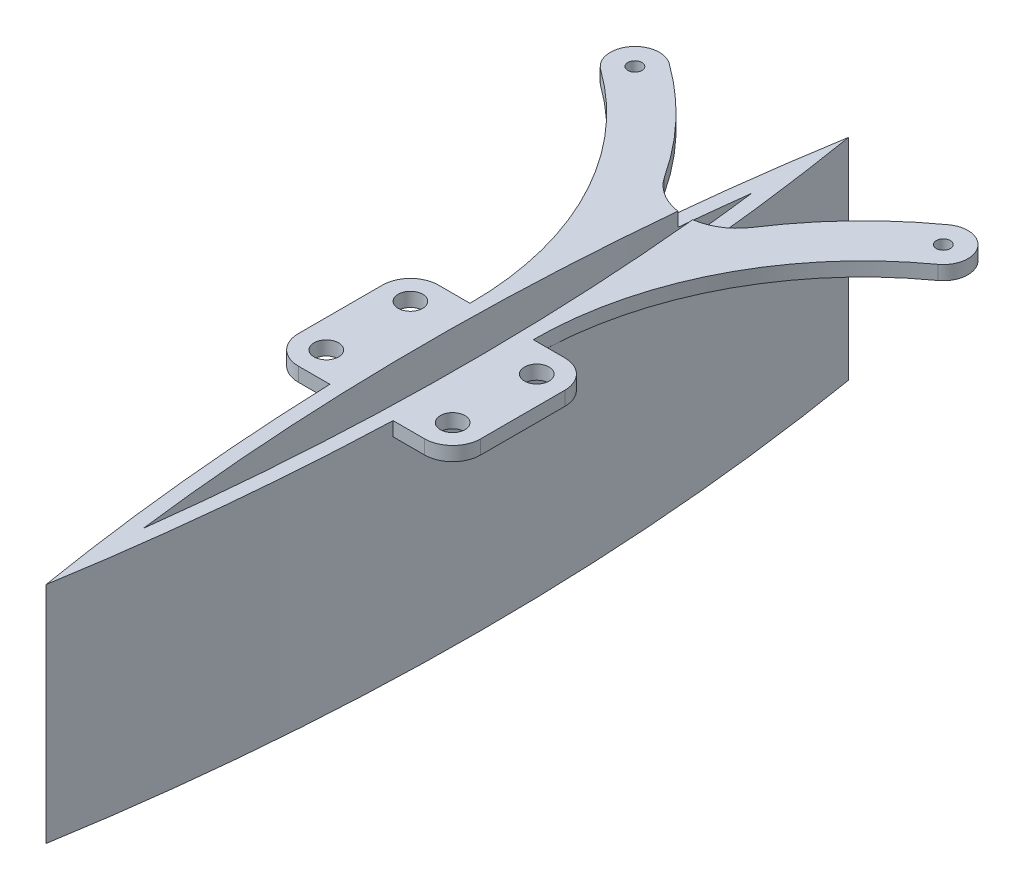
SolidWorks part; units mm, degrees
ref_plane "Plan de face" through (0, 0, 0) normal (0, 0, 1) x (1, 0, 0)
ref_plane "Plan de dessus" through (0, 0, 0) normal (0, 1, 0) x (1, 0, 0)
ref_plane "Plan de droite" through (0, 0, 0) normal (1, 0, 0) x (0, 0, -1)
sketch "Esquisse1" plane through (-102.8474, 0, 18.1348) normal (0, -1, 0) x (-0.9359, 0, 0.3523)
  line L0 (-4.457, -64.9899) -> (-37.8828, 23.8081) construction
  line L1 (-35.783, -7.317) -> (-31.5715, -5.7317)
  line L2 (-18.929, -0.997) -> (-23.1405, -2.5823)
  line L3 (-30.1464, -22.2913) -> (-17.5198, -4.7406) construction
  line L4 (-122.0187, 32.2138) -> (-83.2665, -70.7341) construction
  line L7 (-33.8899, -23.7004) -> (-38.1174, -12.4698)
  line L9 (-24.5257, -24.4495) -> (-28.7372, -26.0348)
  line L11 (-13.7762, -3.3314) -> (-9.5488, -14.5621)
  line L12 (-11.8832, -19.7148) -> (-16.0947, -21.3001)
  line L14 (-65.4719, 25.3159) -> (-23.8989, 40.965) construction
  line L15 (-37.8828, 23.8081) -> (-43.0375, 37.5019) construction
  line L16 (-24.5257, -24.4495) -> (-31.5715, -5.7317) construction
  line L17 (-23.1405, -2.5823) -> (-16.0947, -21.3001) construction
  arc A1 (-24.5257, -24.4495) -> (-4.457, -64.9899) centre (298.5237, 110.2319) ccw
  arc A2 (-61.4801, 29.8533) -> (-63.3071, 23.096) centre (-62.3936, 26.4747) ccw
  arc A3 (-18.2988, 40.0392) -> (-24.13, 43.9118) centre (-21.2144, 41.9755) ccw
  arc A4 (-4.457, -64.9899) -> (-16.0947, -21.3001) centre (-347.7768, -133.0452) ccw
  arc A6 (-35.783, -7.317) -> (-38.1174, -12.4698) centre (-34.3739, -11.0606) ccw
  arc A7 (-33.8899, -23.7004) -> (-28.7372, -26.0348) centre (-30.1464, -22.2913) ccw
  arc A8 (-31.5715, -5.7317) -> (-63.3071, 23.096) centre (-75.5807, -22.2978) ccw
  circle A9 centre (-62.3936, 26.4747) radius 1
  arc A10 (-13.7762, -3.3314) -> (-18.929, -0.997) centre (-17.5198, -4.7406) ccw
  arc A11 (-11.8832, -19.7148) -> (-9.5488, -14.5621) centre (-13.2924, -15.9713) ccw
  circle A16 centre (-34.3739, -11.0606) radius 1.75
  circle A17 centre (-30.1464, -22.2913) radius 1.75
  circle A18 centre (-13.2924, -15.9713) radius 1.75
  circle A19 centre (-17.5198, -4.7406) radius 1.75
  circle A20 centre (-21.2144, 41.9755) radius 1
  arc A21 (-18.2988, 40.0392) -> (-23.1405, -2.5823) centre (20.9106, 13.9994) ccw
  arc A22 (-43.6352, 21.2689) -> (-61.4801, 29.8533) centre (-75.5807, -22.2978) ccw
  arc A24 (-43.6352, 21.2689) -> (-31.8779, 25.6949) centre (-39.2003, 27.3172) ccw
  arc A25 (-24.13, 43.9118) -> (-31.8779, 25.6949) centre (20.9106, 13.9994) ccw
  point P24 (-23.8331, -13.5159)
  dimension "D3" = 22
  dimension "D4" = 7
  dimension "D5" = 7
  dimension "D6" = 2
  dimension "D7" = 2
  dimension "D8" = 7.5
  dimension "D9" = 3.5
  dimension "D10" = 3.5
  dimension "D11" = 3.5
  dimension "D12" = 3.5
  dimension "D15" = 2.25
  dimension "D16" = 2.25
  dimension "D17" = 2.25
  dimension "D18" = 2.25
  dimension "D19" = 45
  dimension "D21" = 9
  dimension "D24" = 18.0001
  dimension "D26" = 700
  dimension "D22" = 350
  dimension "D27" = 55
  dimension "D2" = 22
  dimension "D13" = 12
  dimension "D14" = 9
  dimension "D23" = 18
  dimension "D25" = 12
  dimension "D28" = 4.5
  dimension "D29" = 4.5
extrude "Boss.-Extru.1" add sketch "Esquisse1" along normal blind 2
sketch "Esquisse2" plane through (0, -2, 0) normal (0, -1, 0) x (-1, 0, 0)
  arc A0 (75.7817, 37.1191) -> (75.7807, -77.388) centre (421.0666, -20.1375) ccw
  arc A1 (71.2807, -32.3766) -> (75.7807, -77.388) centre (421.0666, -20.1375) ccw construction
  arc A2 (75.7807, -77.388) -> (75.7817, 37.1191) centre (-269.5042, -20.1314) ccw
  arc A3 (75.7807, -77.388) -> (80.2807, -32.3993) centre (-269.5042, -20.1314) ccw construction
extrude "Boss.-Extru.2" add sketch "Esquisse2" along normal blind 30
sketch "Esquisse3" plane through (0, 0, 0) normal (0, 1, 0) x (1, 0, 0)
  arc A0 (-75.7816, 23.2472) -> (-75.7808, -63.5161) centre (269.5042, -20.1314) ccw
  arc A1 (-80.2807, -32.3993) -> (-75.7807, -77.388) centre (269.5042, -20.1314) ccw construction
  arc A2 (-75.7808, -63.5161) -> (-75.7816, 23.2472) centre (-421.0666, -20.1375) ccw
  arc A3 (-75.7807, -77.388) -> (-71.2807, -32.3766) centre (-421.0666, -20.1375) ccw construction
  dimension "D1" = 2
  dimension "D2" = 2
extrude "Enlèv. mat.-Extru.1" cut sketch "Esquisse3" against normal blind 30
